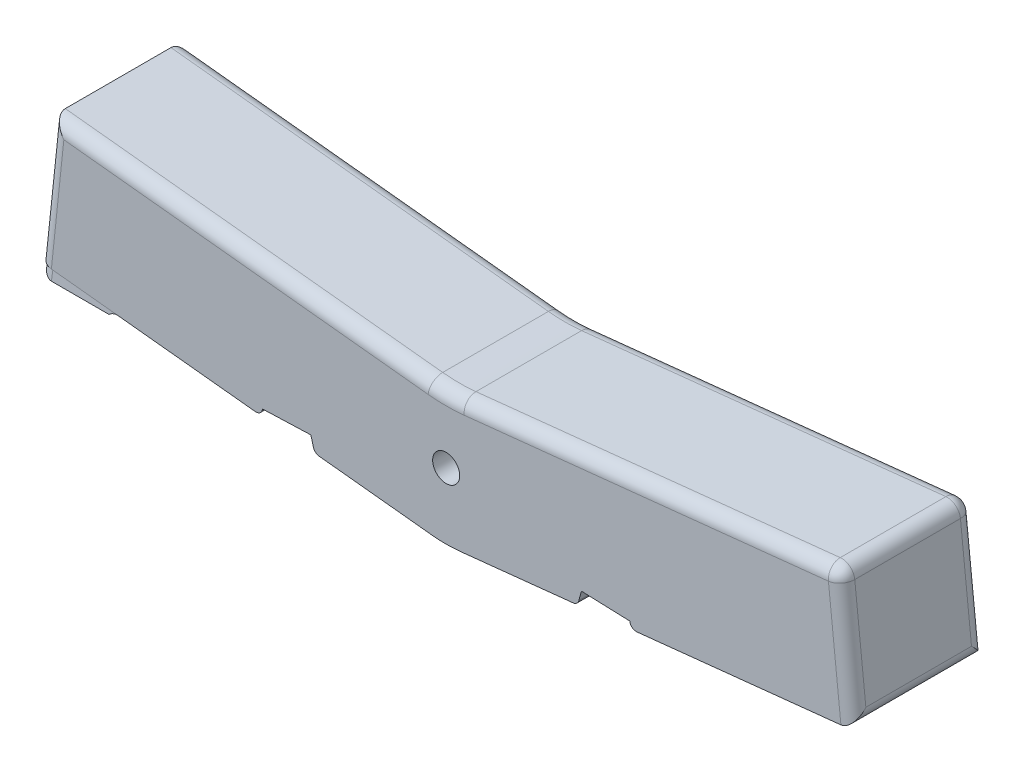
SolidWorks part; units mm, degrees
ref_plane "Front" through (0, 0, 0) normal (0, 0, 1) x (1, 0, 0)
ref_plane "Top" through (0, 0, 0) normal (0, 1, 0) x (1, 0, 0)
ref_plane "Right" through (0, 0, 0) normal (1, 0, 0) x (0, 0, -1)
sketch "Sketch1" plane through (0, 0, 0) normal (0, 0, 1) x (1, 0, 0)
  line L0 (0, -55) -> (0, 55) construction
  line L1 (-2.6632, 0.14) -> (-78.4432, 8.1296)
  line L2 (2.6632, 0.14) -> (78.4432, 8.1296)
  line L3 (-78.4432, 8.1296) -> (-75.78, 33.3896)
  line L4 (-75.78, 33.3896) -> (0, 25.4)
  line L5 (78.4432, 8.1296) -> (75.78, 33.3896)
  line L6 (75.78, 33.3896) -> (0, 25.4)
  arc A1 (2.6632, 0.14) -> (-2.6632, 0.14) centre (0, 25.4) cw
  dimension "D1" = 25.4
  dimension "D2" = 76.2
  dimension "D3" = 25.4
extrude "Boss-Extrude1" add sketch "Sketch1" along normal blind 25.4
sketch "Sketch2" plane through (0, 0, 25.4) normal (0, 0, 1) x (1, 0, 0)
  line L0 (0, -55) -> (0, 55) construction
  circle A0 centre (0, 12.7) radius 2.6
  dimension "D1" = 5.2
  dimension "D2" = 12.7
extrude "Cut-Extrude1" cut sketch "Sketch2" against normal through all
sketch "Sketch8" plane through (0, 0, 0) normal (0, 1, 0) x (1, 0, 0)
  line L1 (-78.4432, -25.4) -> (-64.851, -25.4)
  line L2 (-78.4432, -25.4) -> (-78.4432, 0)
  line L3 (-78.4432, 0) -> (-64.851, 0)
  line L4 (-2.6632, 0) -> (-78.4432, 0)
  line L5 (-2.6632, 0) -> (-78.4432, 0)
  line L7 (-78.4432, -25.4) -> (-2.6632, -25.4)
  line L12 (-64.851, -25.4) -> (-64.851, 0)
  line L18 (-78.4432, -25.4) -> (-2.6632, -25.4)
  line L20 (-78.4432, 0) -> (-78.4432, -25.4)
  line L21 (-78.4432, 0) -> (-78.4432, -25.4)
  line L22 (-2.6632, -25.4) -> (-2.6632, 0)
  line L23 (-2.6632, -25.4) -> (-2.6632, 0)
  dimension "D1" = 0
extrude "Boss-Extrude3" add sketch "Sketch8" along direction (0, 1, 0) on the side of the normal blind 3.81 draft 4 from offset 5.842 contours L1 L12 L3 L2
fillet "Fillet1" radius 30.48 1 edges at (0, 25.4, 12.7)
fillet "Fillet2" radius 2.54 16 edges at (-39.4879, 29.5633, 0) (0, 25.5689, 0) (-39.4879, 29.5633, 25.4) (0, 25.5689, 25.4) (78.4432, 8.1296, 12.7) (77.1116, 20.7596, 25.4) (75.78, 33.3896, 12.7) (77.1116, 20.7596, 0) (-77.1116, 20.7596, 25.4) (-77.1116, 20.7596, 0) (39.4879, 29.5633, 0) (39.4879, 29.5633, 25.4) (-64.9112, 6.7029, 12.7) (-78.3638, 6.9774, 0.0794) (-78.4432, 5.842, 12.7) (-78.3638, 6.9774, 25.3206)
sketch "Sketch3" [suppressed] plane through (-0.0147, -0.1392, 0) normal (-0.1049, -0.9945, 0) x (0.9945, -0.1049, 0)
  line L0 (-76.3232, 25.4) -> (-76.3232, 0) construction
  line L1 (-76.3232, 25.4) -> (-50.8774, 25.4)
  line L2 (-76.3232, 25.4) -> (-76.3232, 0)
  line L3 (-76.3232, 0) -> (-50.8774, 0)
  line L4 (-50.8774, 25.4) -> (-50.8774, 0)
  line L9 (-2.6632, 25.4) -> (-76.3232, 25.4)
  line L10 (-76.3232, 25.4) -> (-76.3232, 0)
  line L11 (-76.3232, 0) -> (-2.6632, 0)
  line L12 (-2.6632, 0) -> (-2.6632, 25.4)
  line L13 (-2.6632, 25.4) -> (-76.3232, 25.4)
  line L14 (-76.3232, 25.4) -> (-76.3232, 0)
  line L15 (-76.3232, 0) -> (-2.6632, 0)
  line L16 (-2.6632, 0) -> (-2.6632, 25.4)
  point P8 (-76.3232, 12.7)
  point P10 (-76.3232, 12.7)
  dimension "D1" = 0
extrude "Boss-Extrude2" [suppressed] add sketch "Sketch3" along normal blind 2.54 contours L2 L1 L4 L3
sketch "Sketch4" plane through (-0.0147, -0.1392, 0) normal (-0.1049, -0.9945, 0) x (0.9945, -0.1049, 0)
  line L0 (-2.6632, 25.4) -> (-2.6632, 0) construction
  line L1 (-33.1432, 20.8611) -> (-28.0632, 20.8611)
  line L2 (-33.1432, 20.8611) -> (-33.1432, 3.4455)
  line L3 (-33.1432, 3.4455) -> (-28.0632, 3.4455)
  line L4 (-28.0632, 20.8611) -> (-28.0632, 3.4455)
  line L5 (18.3643, 0) -> (-18.3643, 0) construction
  line L6 (-76.3232, 25.4) -> (-2.6632, 25.4) construction
  circle A0 centre (-30.4774, 17.526) radius 2.15
  circle A1 centre (-30.4774, 7.874) radius 2.15
  dimension "D2" = 4.3
  dimension "D4" = 7.874
  dimension "D5" = 7.874
  dimension "D1" = 25.4
  dimension "D3" = 5.08
extrude "Cut-Extrude2" cut sketch "Sketch4" against normal blind 5.5 contours A0 | A1 | L2 L1 L4 L3
sketch "Sketch5" plane through (0.0147, -0.1392, 0) normal (0.1049, -0.9945, 0) x (0.9945, 0.1049, 0)
  line L0 (2.6632, 25.4) -> (2.6632, 0) construction
  line L1 (28.0632, 21.6214) -> (32.9851, 21.6214)
  line L2 (28.0632, 21.6214) -> (28.0632, 3.7786)
  line L3 (28.0632, 3.7786) -> (32.9851, 3.7786)
  line L4 (32.9851, 21.6214) -> (32.9851, 3.7786)
  line L6 (18.3643, 0) -> (-18.3643, 0) construction
  line L7 (2.6632, 25.4) -> (76.3232, 25.4) construction
  circle A0 centre (30.5152, 17.526) radius 2.15
  circle A1 centre (30.5152, 7.874) radius 2.15
  point P12 (28.0632, 12.7)
  dimension "D3" = 4.3
  dimension "D1" = 4.9219
  dimension "D2" = 25.4
  dimension "D4" = 12.7
  dimension "D5" = 7.874
  dimension "D6" = 7.874
extrude "Cut-Extrude3" cut sketch "Sketch5" against normal blind 5.6 contours A0 | A1
sketch "Sketch6" plane through (0, 0, 25.4) normal (0, 0, 1) x (1, 0, 0)
  line L1 (0, -14.1653) -> (0, 14.1653) construction
  line L7 (-25.2849, 2.525) -> (-26.0188, 5.1921)
  line L8 (25.2849, 2.525) -> (26.0188, 5.1921)
  line L9 (35.4541, 3.5972) -> (25.2849, 2.525)
  line L10 (35.3212, 4.8574) -> (35.4541, 3.5972)
  line L11 (26.0188, 5.1921) -> (35.3212, 4.8574)
  line L12 (-35.4541, 3.5972) -> (-25.2849, 2.525)
  line L13 (-35.3212, 4.8574) -> (-35.4541, 3.5972)
  line L14 (-26.0188, 5.1921) -> (-35.3212, 4.8574)
  line L15 (2.6632, 0.14) -> (75.9172, 7.8633) construction
extrude "Cut-Extrude4" cut sketch "Sketch6" against normal through all
fillet "Fillet3" radius 1.27 4 edges at (35.4541, 3.5972, 12.7) (25.2849, 2.525, 12.7) (-35.4541, 3.5972, 12.7) (-25.2849, 2.525, 12.7)
sketch "Sketch9" plane through (-0.2202, 6.1203, 0) normal (0.036, -0.9994, 0) x (0.9994, 0.036, 0)
  line L1 (-32.1695, 21.614) -> (-27.2494, 21.614)
  line L2 (-32.1695, 21.614) -> (-32.1695, 2.0828)
  line L3 (-32.1695, 2.0828) -> (-27.2494, 2.0828)
  line L4 (-27.2494, 21.614) -> (-27.2494, 2.0828)
extrude "Boss-Extrude4" add sketch "Sketch9" against normal blind 1
sketch "Sketch10" plane through (0.2202, 6.1203, 0) normal (-0.036, -0.9994, 0) x (0.9994, -0.036, 0)
  line L1 (27.3919, 21.5973) -> (32.185, 21.5973)
  line L2 (27.3919, 21.5973) -> (27.3919, 4.7185)
  line L3 (27.3919, 4.7185) -> (32.185, 4.7185)
  line L4 (32.185, 21.5973) -> (32.185, 4.7185)
extrude "Boss-Extrude5" add sketch "Sketch10" against normal blind 1
